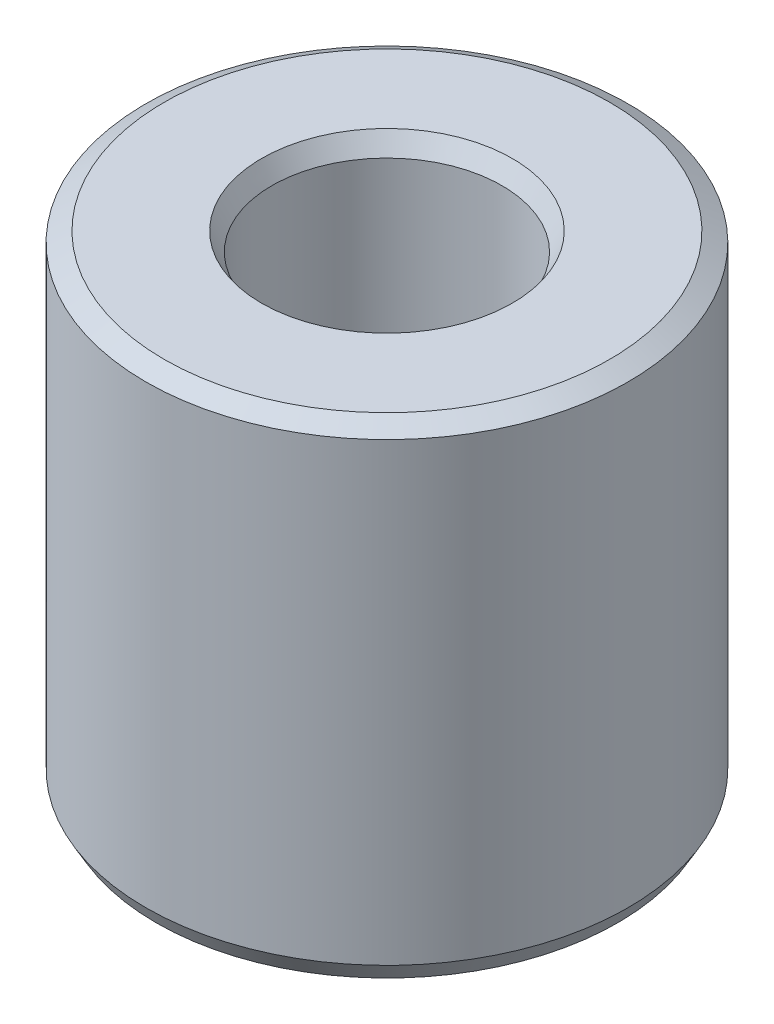
SolidWorks part; units mm, degrees
ref_plane "Front Plane" through (0, 0, 0) normal (0, 0, 1) x (1, 0, 0)
ref_plane "Top Plane" through (0, 0, 0) normal (0, 1, 0) x (1, 0, 0)
ref_plane "Right Plane" through (0, 0, 0) normal (1, 0, 0) x (0, 0, -1)
sketch "Sketch1" plane through (0, 0, 0) normal (0, 1, 0) x (1, 0, 0)
  circle A0 centre (0, 0) radius 22.5
  dimension "SLEEVE_OD" = 45
extrude "Boss-Extrude1" add sketch "Sketch1" along normal blind 45.1802
sketch "Sketch2" plane through (0, 0, 0) normal (0, 1, 0) x (1, 0, 0)
  circle A0 centre (0, 0) radius 10.7359
  dimension "BORE_D" = 21.4718
extrude "Cut-Extrude1" cut sketch "Sketch2" along normal through all
chamfer "Chamfer1" distance 0.9688 angle 60.446 4 edges at (0, 45.1802, 10.7359) (0, 0, 10.7359) (0, 0, 22.5) (0, 45.1802, 22.5) first distance on face at (0, 45.1802, 10.7359) first distance on face at (0, 0, 10.7359) first distance on face at (0, 45.1802, 22.5)
